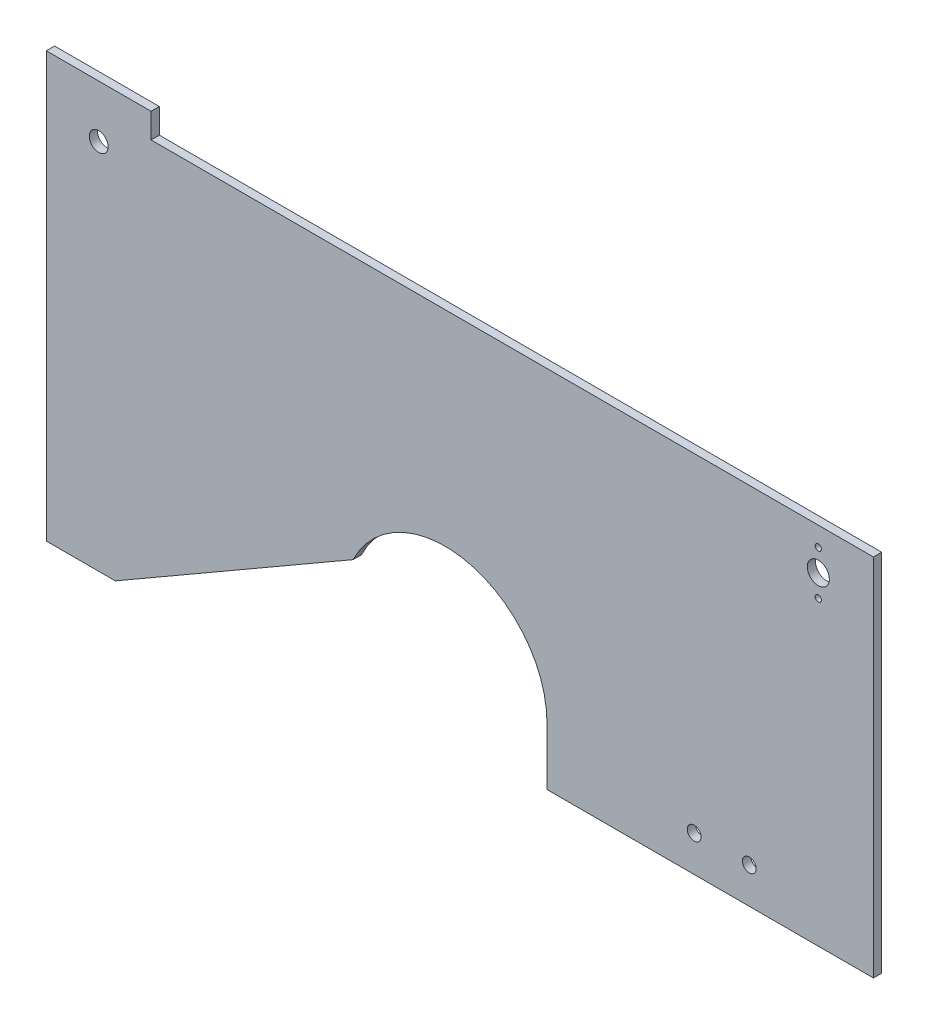
SolidWorks part; units mm, degrees
ref_plane "Front Plane" through (0, 0, 0) normal (0, 0, 1) x (1, 0, 0)
ref_plane "Top Plane" through (0, 0, 0) normal (0, 1, 0) x (1, 0, 0)
ref_plane "Right Plane" through (0, 0, 0) normal (1, 0, 0) x (0, 0, -1)
sketch "Sketch2" plane through (0, 0, 0) normal (0, 0, 1) x (1, 0, 0)
  line L0 (25.0304, 0) -> (111.2865, 49.8)
  line L1 (0, 0) -> (25.0304, 0)
  line L2 (0, 0) -> (0, 154)
  line L4 (300, 0) -> (300, 145)
  line L5 (181.6, 33.7) -> (181.6, 0)
  line L6 (181.6, 0) -> (300, 0)
  line L7 (19, 135) -> (19, 164.3674) construction
  line L11 (38, 145) -> (300, 145)
  line L12 (0, 154) -> (19, 154)
  line L13 (19, 154) -> (38, 154)
  line L14 (38, 154) -> (38, 145)
  line L15 (19, 135) -> (50019, 135) construction
  line L20 (19, 135) -> (19, -49865) construction
  circle A0 centre (19, 135) radius 3.425
  arc A1 (181.6, 33.7) -> (111.2865, 49.8) centre (144.6, 33.7) ccw
  point P19 (19, 154)
  dimension "D3" = 135
  dimension "D4" = 19
  dimension "D5" = 6.85
  dimension "D6" = 74
  dimension "D7" = 155.4
  dimension "D8" = 33.7
  dimension "D1" = 300
  dimension "D2" = 154
  dimension "D9" = 30
  dimension "D10" = 99.6
  dimension "D11" = 19
extrude "Boss-Extrude2" add sketch "Sketch2" along normal blind 3
sketch "Sketch3" plane through (0, 0, 3) normal (0, 0, 1) x (1, 0, 0)
  line L0 (300, 0) -> (300, 145) construction
  line L1 (181.6, 0) -> (300, 0)
  line L2 (181.6, 0) -> (181.6, 12.75)
  line L3 (181.6, 12.75) -> (300, 12.75)
  line L4 (300, 0) -> (300, 12.75)
  dimension "D1" = 12.75
extrude "Cut-Extrude1" cut sketch "Sketch3" against normal through all
sketch "Sketch4" plane through (0, 0, 3) normal (0, 0, 1) x (1, 0, 0)
  line L0 (19, 135) -> (19, -49865) construction
  line L1 (19, 135) -> (-49981, 135) construction
sketch "Sketch5" plane through (0, 0, 3) normal (0, 0, 1) x (1, 0, 0)
  line L0 (300, 12.75) -> (300, 145) construction
  line L1 (300, 12.75) -> (181.6, 12.75) construction
  line L2 (300, 145) -> (38, 145) construction
  circle A0 centre (254.98, 25.75) radius 2.5
  circle A1 centre (234.98, 25.75) radius 2.5
  circle A2 centre (280, 130) radius 4
  circle A3 centre (280, 138) radius 1.125
  circle A4 centre (280, 122) radius 1.125
  dimension "D1" = 5
  dimension "D2" = 45.02
  dimension "D3" = 13
  dimension "D4" = 5
  dimension "D5" = 20
  dimension "D6" = 13
  dimension "D9" = 8
  dimension "D10" = 2.25
  dimension "D11" = 8
  dimension "D12" = 20
  dimension "D13" = 8
  dimension "D14" = 20
  dimension "D15" = 2.25
  dimension "D7" = 20
  dimension "D8" = 15
extrude "Cut-Extrude2" cut sketch "Sketch5" against normal through all
